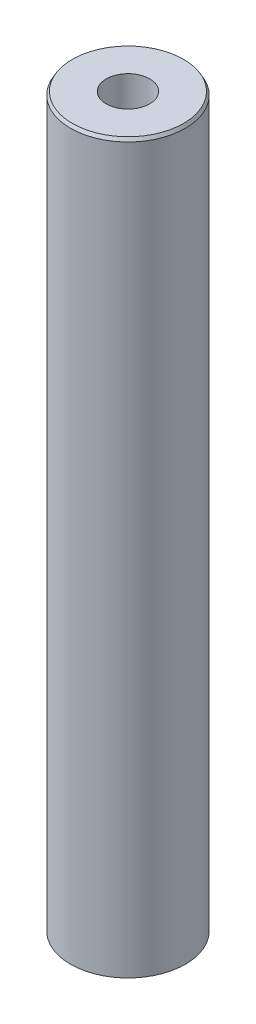
SolidWorks part; units mm, degrees
ref_plane "Front Plane" through (0, 0, 0) normal (0, 0, 1) x (1, 0, 0)
ref_plane "Top Plane" through (0, 0, 0) normal (0, 1, 0) x (1, 0, 0)
ref_plane "Right Plane" through (0, 0, 0) normal (1, 0, 0) x (0, 0, -1)
sketch "Sketch1" plane through (0, 0, 0) normal (0, 1, 0) x (1, 0, 0)
  circle A0 centre (0, 0) radius 45
  dimension "SHAFT_OD" = 90
extrude "Boss-Extrude1" add sketch "Sketch1" along normal blind 571.0177
sketch "Sketch2" plane through (0, 0, 0) normal (0, 1, 0) x (1, 0, 0)
  circle A0 centre (0, 0) radius 17.0118
  dimension "BORE_D" = 34.0235
extrude "Cut-Extrude1" cut sketch "Sketch2" along normal through all
chamfer "Chamfer1" distance 2.5398 angle 30 2 edges at (0, 571.0177, 45) (0, 0, 45) first distance on face at (0, 571.0177, 45) first distance on face at (0, 0, 17.0118)
